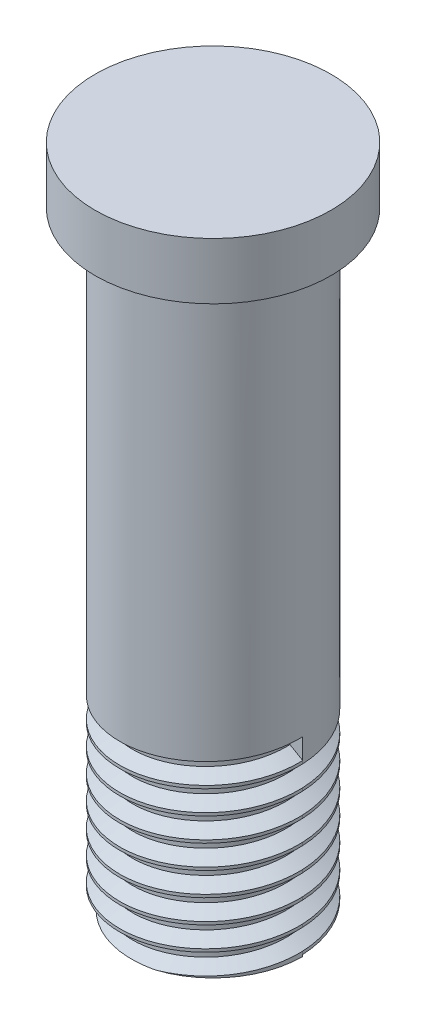
SolidWorks part; units mm, degrees
ref_plane "Front Plane" through (0, 0, 0) normal (0, 0, 1) x (1, 0, 0)
ref_plane "Top Plane" through (0, 0, 0) normal (0, 1, 0) x (1, 0, 0)
ref_plane "Right Plane" through (0, 0, 0) normal (1, 0, 0) x (0, 0, -1)
sketch "Sketch1" plane through (0, 0, 0) normal (0, 1, 0) x (1, 0, 0)
  circle A0 centre (0, 0) radius 4.75
  dimension "D1" = 9.5
extrude "Boss-Extrude1" add sketch "Sketch1" along normal blind 32
sketch "Sketch2" plane through (0, 32, 0) normal (0, 1, 0) x (1, 0, 0)
  circle A0 centre (0, 0) radius 6.25
  circle A1 centre (0, 0) radius 4.75 construction
  dimension "D1" = 1.5
extrude "Boss-Extrude2" add sketch "Sketch2" along normal blind 3
thread "Thread1" pitch 1.25 method cut profile "Thread Profile1" start angle 0, offset 1, length 10, pitch 1.25, diameter 9.5
ref_plane "Plane1" through (4.75, -1, 0) normal (0, 0, 1) x (1, 0, 0)
sketch "Thread Profile1" plane through (4.75, -1, 0) normal (0, 0, 1) x (1, 0, 0)
  line L0 (0, 0) -> (0, 1.25) construction
  line L11 (0, 0) -> (0, 1.0937)
  line L12 (0, 1.0937) -> (-0.6766, 0.7031)
  line L13 (-0.6766, 0.7031) -> (-0.6766, 0.3906)
  line L15 (-0.6766, 0.3906) -> (0, 0)
  line L17 (-0.6766, 0.5469) -> (0, 0.5469) construction
  point P2 (0, 0)
  dimension "Pitch" = 1.25
  dimension "Profile_Angle" = 60
  dimension "Profile_Land" = 0.3125
  dimension "Profile_Height" = 0.6766
